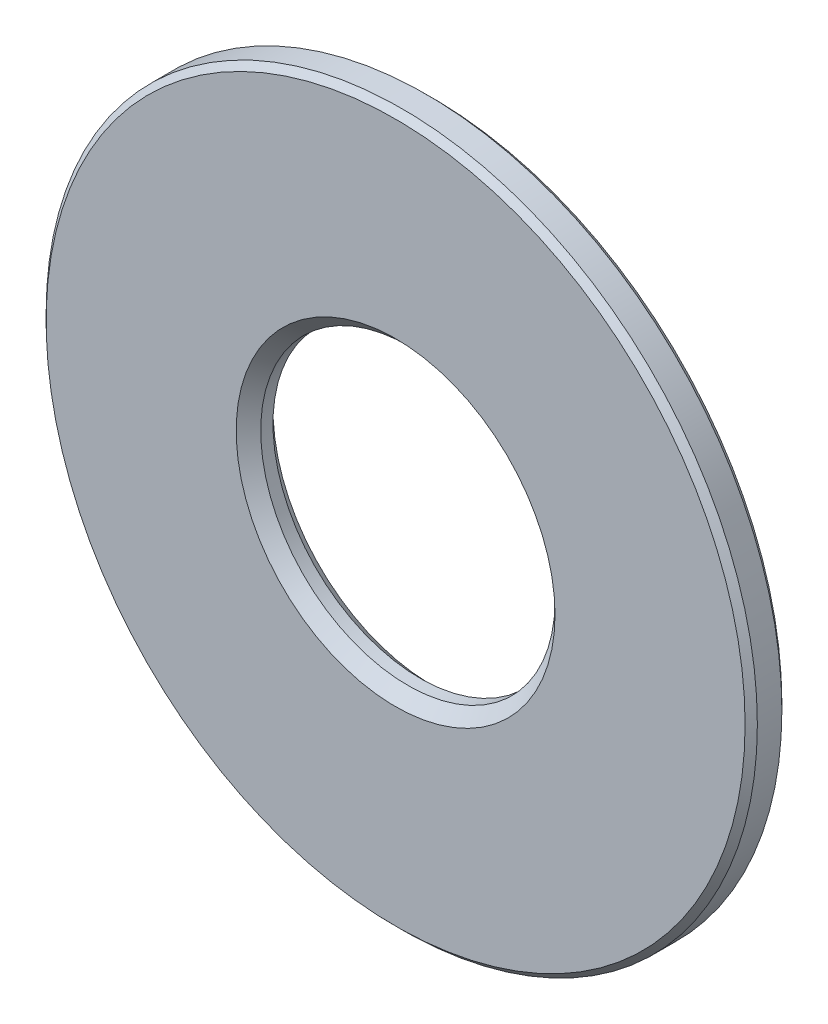
SolidWorks part; units mm, degrees
material "Plain Carbon Steel"
ref_plane "Front" through (0, 0, 0) normal (0, 0, 1) x (1, 0, 0)
ref_plane "Top" through (0, 0, 0) normal (0, 1, 0) x (1, 0, 0)
ref_plane "Right" through (0, 0, 0) normal (1, 0, 0) x (0, 0, -1)
ref_axis "Axis1" through (-84.4107, 0, 0) along (1, 0, 0)
ref_axis "Axis2" through (0, 64.3378, 0) along (0, -1, 0)
ref_axis "Axis3" through (0, 0, -102.329) along (0, 0, 1)
sketch "Sketch1" plane through (0, 0, 0) normal (0, 0, 1) x (1, 0, 0)
  circle A0 centre (0, 0) radius 29
  circle A1 centre (0, 0) radius 12
  dimension "D1" = 58
  dimension "D2" = 24
extrude "Boss-Extrude1" add sketch "Sketch1" along normal blind 3
chamfer "Chamfer1" distance 1 angle 45 2 edges at (12, 0, 0) (12, 0, 3)
chamfer "Chamfer2" distance 0.5 angle 45 2 edges at (29, 0, 0) (29, 0, 3)
ref_plane "back" through (0, 0, 3) normal (0, 0, 1) x (1, 0, 0)
